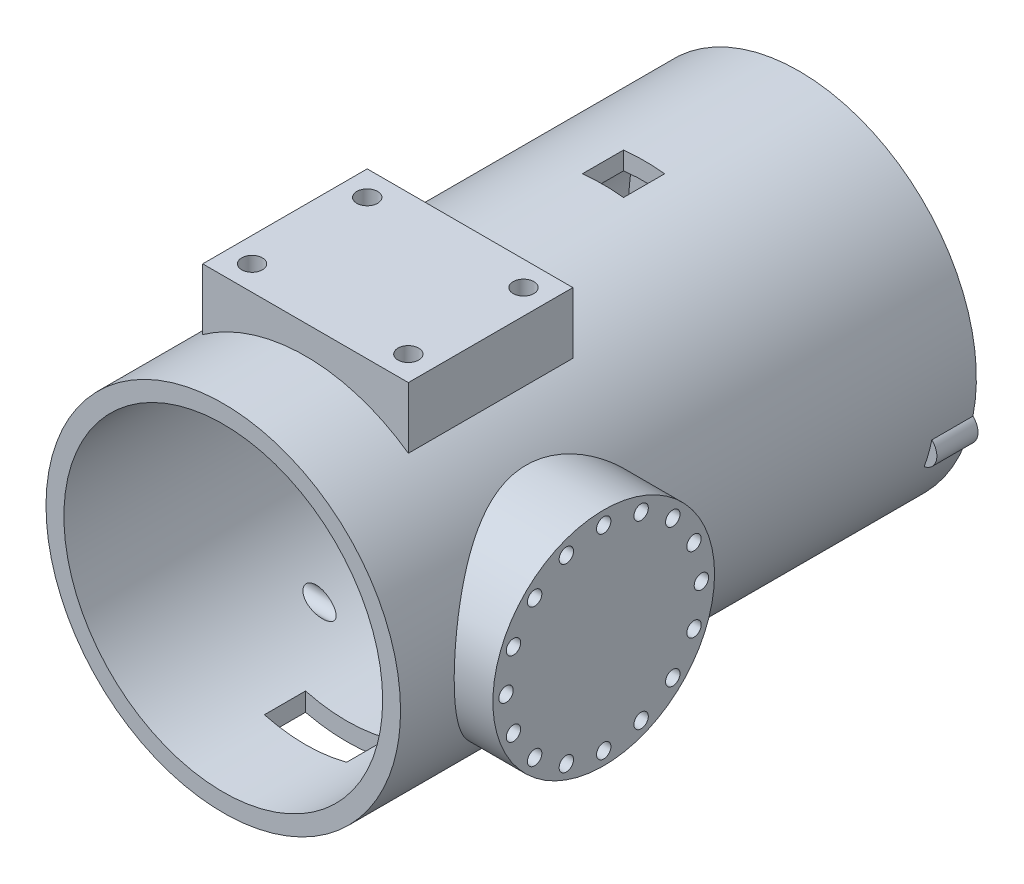
SolidWorks part; units mm, degrees
other "Markup1"
sketch "Sketch14" plane through (-43.1, 43.1, 140) normal (-0.1765, 0.0048, 0.9843) x (0.9842, -0.0149, 0.1765)
other "Markup2"
sketch "Sketch23" plane through (45.1, -43.1, 140) normal (0.9491, -0.0629, 0.3087) x (0.311, 0.031, -0.9499)
ref_plane "Front Plane" through (0, 0, 0) normal (0, 0, 1) x (1, 0, 0)
ref_plane "Top Plane" through (0, 0, 0) normal (0, 1, 0) x (1, 0, 0)
ref_plane "Right Plane" through (0, 0, 0) normal (1, 0, 0) x (0, 0, -1)
sketch "Sketch1" plane through (0, 0, 0) normal (0, 0, 1) x (1, 0, 0)
  circle A1 centre (0, 0) radius 43.1
  dimension "D1" = 86.2
extrude "Main Body" add sketch "Sketch1" along normal blind 140
ref_plane "Plane1" through (0, 43.1, 0) normal (0, 1, 0) x (1, 0, 0)
sketch "Sketch34" [suppressed] plane through (0, 43.1, 0) normal (0, 1, 0) x (1, 0, 0)
  line L6 (-5, -13) -> (5, -13)
  line L8 (-5, -13) -> (-5, -3)
  line L9 (-5, -3) -> (5, -3)
  line L10 (5, -13) -> (5, -3)
  line L11 (-5, -13) -> (5, -3) construction
  line L12 (-5, -3) -> (5, -13) construction
  point P0 (0, -8)
  dimension "D1" = 8
  dimension "D2" = 10
  dimension "D3" = 10
sketch "Sketch6" plane through (0, 43.1, 0) normal (0, 1, 0) x (1, 0, 0)
  line L2 (-5, -47.7) -> (5, -47.7)
  line L3 (-5, -47.7) -> (-5, -37.7)
  line L4 (-5, -37.7) -> (5, -37.7)
  line L5 (5, -47.7) -> (5, -37.7)
  line L6 (-5, -47.7) -> (5, -37.7) construction
  line L7 (-5, -37.7) -> (5, -47.7) construction
  point P2 (0, -42.7)
  dimension "D2" = 10
  dimension "D1" = 42.7
  dimension "D3" = 10
extrude "Cut-Extrude3" cut sketch "Sketch6" against normal through all
ref_plane "Plane2" through (52.5, 0, 0) normal (1, 0, 0) x (0, 0, -1)
sketch "Sketch8" plane through (52.5, 0, 0) normal (1, 0, 0) x (0, 0, -1)
  circle A0 centre (-100, 0) radius 26.95
  dimension "D1" = 53.9
  dimension "D2" = 100
extrude "Boss-Extrude2" add sketch "Sketch8" against normal blind 20
mirror "Mirror1" [suppressed] about plane through (0, 0, 0) normal (1, 0, 0)
ref_plane "Plane3" through (0, 50, 0) normal (0, 1, 0) x (1, 0, 0)
sketch "Sketch33" plane through (0, 50, 0) normal (0, 1, 0) x (1, 0, 0)
  line L1 (-25, -120) -> (25, -120)
  line L2 (-25, -120) -> (-25, -80)
  line L3 (-25, -80) -> (25, -80)
  line L4 (25, -120) -> (25, -80)
  line L5 (-25, -120) -> (25, -80) construction
  line L6 (-25, -80) -> (25, -120) construction
  point P0 (0, -100)
  dimension "D1" = 100
  dimension "D2" = 40
  dimension "D3" = 50
extrude "Boss-Extrude11" add sketch "Sketch33" against normal blind 22
sketch "Sketch35" plane through (0, 50, 0) normal (0, 1, 0) x (1, 0, 0)
  line L0 (-25, -120) -> (-25, -80) construction
  line L1 (25, -120) -> (25, -80) construction
  line L2 (25, -80) -> (-25, -80) construction
  line L3 (-25, -120) -> (25, -120) construction
  circle A0 centre (-19, -86) radius 2.525
  circle A1 centre (19, -86) radius 2.525
  circle A2 centre (-19, -114) radius 2.525
  circle A3 centre (19, -114) radius 2.525
  dimension "D1" = 5.05
  dimension "D2" = 6
  dimension "D3" = 6
  dimension "D4" = 6
  dimension "D5" = 6
extrude "Cut-Extrude14" cut sketch "Sketch35" against normal blind 4
sketch "Sketch5" plane through (0, 0, 140) normal (0, 0, 1) x (1, 0, 0)
  circle A0 centre (0, 0) radius 32
  dimension "D1" = 64
extrude "Hole 1" cut sketch "Sketch5" against normal through all
sketch "Sketch10" plane through (0, 0, 0) normal (0, 1, 0) x (1, 0, 0)
  line L0 (43.1, 0) -> (-43.1, 0) construction
  line L1 (-10, -120) -> (10, -120)
  line L2 (-10, -120) -> (-10, -110)
  line L3 (-10, -110) -> (10, -110)
  line L4 (10, -120) -> (10, -110)
  line L5 (-10, -120) -> (10, -110) construction
  line L6 (-10, -110) -> (10, -120) construction
  point P0 (0, -115)
  point P7 (-10, -115)
  dimension "D1" = 110
  dimension "D2" = 10
  dimension "D3" = 20
extrude "Motor Wire Hole" cut sketch "Sketch10" against normal through all
sketch "Sketch27" plane through (0, 0, 0) normal (1, 0, 0) x (0, 0, -1)
  line L1 (-100, -36.5) -> (-60, -36.5)
  line L2 (-100, -36.5) -> (-100, -27.5)
  line L3 (-100, -27.5) -> (-60, -27.5)
  line L4 (-60, -36.5) -> (-60, -27.5)
  dimension "D1" = 60
  dimension "D2" = 27.5
  dimension "D3" = 40
  dimension "D4" = 9
extrude "Boss-Extrude9" add sketch "Sketch27" along normal blind 33 and the other way blind 33
sketch "Sketch11" plane through (0, 0, 0) normal (1, 0, 0) x (0, 0, -1)
  circle A0 centre (-65, -32) radius 2.25
  circle A1 centre (-95, -32) radius 2.25
  dimension "D3" = 4.5
  dimension "D1" = 65
  dimension "D2" = 32
  dimension "D4" = 30
extrude "Cut-Extrude6" cut sketch "Sketch11" against normal through all both and the other way through all
sketch "Sketch28" plane through (-33, 0, 0) normal (-1, 0, 0) x (0, 0, 1)
  line L0 (62.8927, -28.35) -> (67.1073, -28.35)
  line L1 (67.1073, -28.35) -> (69.2147, -32)
  line L2 (69.2147, -32) -> (67.1073, -35.65)
  line L3 (67.1073, -35.65) -> (62.8927, -35.65)
  line L4 (62.8927, -35.65) -> (60.7853, -32)
  line L6 (60.7853, -32) -> (62.8927, -28.35)
  line L7 (92.8927, -28.35) -> (97.1073, -28.35)
  line L8 (97.1073, -28.35) -> (99.2147, -32)
  line L9 (99.2147, -32) -> (97.1073, -35.65)
  line L10 (97.1073, -35.65) -> (92.8927, -35.65)
  line L11 (92.8927, -35.65) -> (90.7853, -32)
  line L12 (90.7853, -32) -> (92.8927, -28.35)
  circle A0 centre (65, -32) radius 3.65 construction
  circle A1 centre (65, -32) radius 2.25 construction
  circle A2 centre (95, -32) radius 3.65 construction
  circle A3 centre (95, -32) radius 2.25 construction
  dimension "D2" = 7.3
extrude "Cut-Extrude7" cut sketch "Sketch28" against normal blind 3
sketch "Sketch29" plane through (33, 0, 0) normal (1, 0, 0) x (0, 0, -1)
  circle A0 centre (-95, -32) radius 3.6
  circle A1 centre (-65, -32) radius 3.6
  dimension "D1" = 7.2
extrude "Cut-Extrude8" cut sketch "Sketch29" against normal blind 4
sketch "Sketch2" plane through (0, 0, 140) normal (0, 0, 1) x (1, 0, 0)
  circle A0 centre (0, 0) radius 38.75
  dimension "D1" = 77.5
extrude "Cut-Extrude5" cut sketch "Sketch2" against normal blind 135
sketch "Sketch9" plane through (0, 0, 5) normal (0, 0, 1) x (1, 0, 0)
  circle A0 centre (0, 0) radius 38.1
  circle A1 centre (0, 0) radius 36.44
  dimension "D1" = 76.2
  dimension "D2" = 1.66
extrude "Boss-Extrude3" add sketch "Sketch9" along normal blind 10
extrude "Cut-Extrude13" [suppressed] cut sketch "Sketch34" against normal blind 15
sketch "Sketch30" plane through (52.5, 0, 0) normal (1, 0, 0) x (0, 0, -1)
  line L0 (-100, 23.75) -> (-100, 0) construction
  circle A0 centre (-100, 0) radius 23.75 construction
  circle A1 centre (-100, 23.75) radius 1.75
  circle A2 centre (-90.9113, 21.9421) radius 1.75
  circle A3 centre (-83.2062, 16.7938) radius 1.75
  circle A4 centre (-78.0579, 9.0887) radius 1.75
  circle A5 centre (-76.25, 0) radius 1.75
  circle A6 centre (-78.0579, -9.0887) radius 1.75
  circle A7 centre (-83.2062, -16.7938) radius 1.75
  circle A8 centre (-90.9113, -21.9421) radius 1.75
  circle A9 centre (-100, -23.75) radius 1.75
  circle A10 centre (-109.0887, -21.9421) radius 1.75
  circle A11 centre (-116.7938, -16.7938) radius 1.75
  circle A12 centre (-121.9421, -9.0887) radius 1.75
  circle A13 centre (-123.75, 0) radius 1.75
  circle A14 centre (-121.9421, 9.0887) radius 1.75
  circle A15 centre (-116.7938, 16.7938) radius 1.75
  circle A16 centre (-109.0887, 21.9421) radius 1.75
  point P38 (-100, 0)
  dimension "D1" = 47.5
  dimension "D2" = 3.5
  dimension "D3" = 16
extrude "Cut-Extrude9" cut sketch "Sketch30" against normal up to surface (21.8814 mm away) up to face at (21.9823, -31.9114, 97.2483)
sketch "Sketch31" plane through (52.5, 0, 0) normal (1, 0, 0) x (0, 0, -1)
  line L0 (0, -43.1) -> (0, 43.1) construction
  line L1 (0, -15) -> (-10, -15)
  line L2 (0, -15) -> (0, -7.5)
  line L3 (0, -7.5) -> (-10, -7.5)
  line L4 (-10, -15) -> (-10, -7.5)
  dimension "D1" = 15
  dimension "D2" = 7.5
  dimension "D3" = 10
extrude "Boss-Extrude10" add sketch "Sketch31" against normal up to body from offset 9 offset against normal yes
sketch "Sketch32" plane through (0, 0, 0) normal (0, 0, -1) x (-1, 0, 0)
  line L0 (-43.5, -11.25) -> (-29.9573, -11.25) construction
  line L1 (-43.5, -15) -> (-43.5, -7.5) construction
  line L3 (-42.4424, -7.5) -> (-43.5, -7.5) construction
  line L5 (-43.5, -15) -> (-43.5, -7.5)
  line L6 (-43.5, -7.5) -> (-42.4424, -7.5)
  circle A0 centre (0, 0) radius 32 construction
  arc A2 (-40.4056, -15) -> (-42.4424, -7.5) centre (0, 0) ccw construction
  arc A3 (-40.4056, -15) -> (-42.2658, -8.4385) centre (-39.6806, -11.25) cw
  arc A4 (-42.2658, -8.4385) -> (-42.4424, -7.5) centre (0, 0) cw
  line M3 (-42.4424, -7.5) -> (-43.5, -7.5)
  line M4 (-43.5, -7.5) -> (-43.5, -15)
  line M5 (-43.5, -15) -> (-40.4056, -15)
extrude "Cut-Extrude10" cut sketch "Sketch32" against normal up to surface (10 mm away) contours M4 M3 | L5 M5 region at (43.0347, -8.5479, 0) region at (42.7123, -14.1508, 0) up to face at (42.5043, -11.2615, 10)
